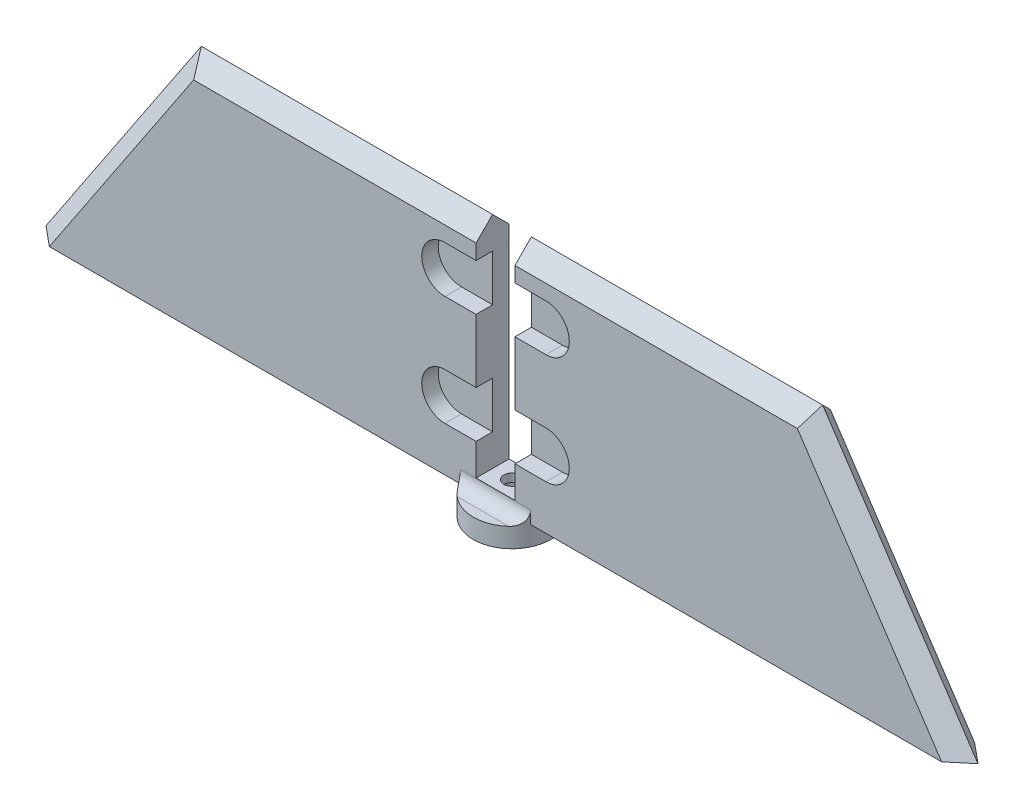
SolidWorks part; units mm, degrees
ref_plane "Alzado" through (0, 0, 0) normal (0, 0, 1) x (1, 0, 0)
ref_plane "Planta" through (0, 0, 0) normal (0, 1, 0) x (1, 0, 0)
ref_plane "Vista lateral" through (0, 0, 0) normal (1, 0, 0) x (0, 0, -1)
sketch "Croquis1" plane through (0, 0, 0) normal (0, 0, 1) x (1, 0, 0)
  line L0 (60, 0) -> (-60, 0)
  line L1 (-60, 0) -> (-40, 30)
  line L2 (-40, 30) -> (40, 30)
  line L3 (40, 30) -> (60, 0)
  point P4 (0, 0)
  dimension "D1" = 120
  dimension "D2" = 20
  dimension "3" = 30
  dimension "D3" = 20
extrude "Saliente-Extruir1" add sketch "Croquis1" along normal mid plane 4.25
sketch "Croquis2" plane through (0, 0, 0) normal (0, -1, 0) x (1, 0, 0)
  circle A0 centre (0, 0) radius 5
  dimension "D1" = 10
extrude "Saliente-Extruir2" add sketch "Croquis2" along normal blind 2.5
fillet "Redondeo1" radius 1.625 2 edges at (0, 0, -2.125) (0, 0, 2.125)
sketch "Sketch1" plane through (0, -2.5, 0) normal (0, -1, 0) x (1, 0, 0)
  circle A0 centre (0, 0) radius 2.45
  dimension "D1" = 4.9
extrude "Cut-Extrude1" cut sketch "Sketch1" against normal blind 3.1
chamfer "Chamfer1" distance 2.125 angle 45 6 edges at (50, 15, -2.125) (0, 30, -2.125) (-50, 15, -2.125) (50, 15, 2.125) (0, 30, 2.125) (-50, 15, 2.125)
sketch "Sketch2" plane through (0, 0, 2.125) normal (0, 0, 1) x (1, 0, 0)
  line L0 (0, 0.6) -> (0, 1.6) construction
  line L2 (-2.45, 0.6) -> (2.45, 0.6) construction
  line L10 (0, 1.6) -> (0, 30.1) construction
  line L12 (2.5, 1.6743) -> (-2.5, 1.6743)
  line L13 (2.5, 1.6743) -> (2.5, 30.0257)
  line L14 (2.5, 30.0257) -> (-2.5, 30.0257)
  line L15 (-2.5, 1.6743) -> (-2.5, 30.0257)
  line L16 (2.5, 1.6743) -> (-2.5, 30.0257) construction
  line L17 (2.5, 30.0257) -> (-2.5, 1.6743) construction
  point P9 (0, 15.85)
  dimension "D1" = 1
  dimension "D2" = 5
  dimension "D3" = 28.5
extrude "Cut-Extrude2" cut sketch "Sketch2" against normal through all both and the other way through all
sketch "Sketch3" plane through (0, 0.6, 0) normal (0, -1, 0) x (1, 0, 0)
  circle A0 centre (0, 0) radius 1.05
  dimension "D1" = 2.1
extrude "Cut-Extrude3" cut sketch "Sketch3" against normal through all both and the other way through all
sketch "Sketch4" plane through (0, 0, 2.125) normal (0, 0, 1) x (1, 0, 0)
  line L0 (0, 1.6743) -> (0, 30) construction
  line L1 (2.5, 1.6743) -> (-2.5, 1.6743) construction
  line L2 (0, 15.8372) -> (0, 30) construction
  line L3 (0, 15.8372) -> (0, 1.6743) construction
  line L4 (2.5, 15.8372) -> (2.5, 1.6743) construction
  line L5 (2.5, 27.875) -> (2.5, 1.6743) construction
  line L6 (2.5, 15.8372) -> (2.5, 30) construction
  line L7 (2.5, 22.9186) -> (6.5, 22.9186) construction
  line L8 (2.5, 8.7557) -> (6.5, 8.7557) construction
  line L9 (2.5, 8.7557) -> (6.5, 8.7557) construction
  line L10 (2.5, 11.7557) -> (6.5, 11.7557)
  line L11 (2.5, 5.7557) -> (6.5, 5.7557)
  line L12 (2.5, 22.9186) -> (6.5, 22.9186) construction
  line L13 (2.5, 25.9186) -> (6.5, 25.9186)
  line L14 (2.5, 19.9186) -> (6.5, 19.9186)
  line L15 (-2.5, 8.7557) -> (-6.5, 8.7557) construction
  line L16 (-2.5, 11.7557) -> (-6.5, 11.7557)
  line L17 (-2.5, 5.7557) -> (-6.5, 5.7557)
  line L18 (-2.5, 22.9186) -> (-6.5, 22.9186) construction
  line L19 (-2.5, 25.9186) -> (-6.5, 25.9186)
  line L20 (-2.5, 19.9186) -> (-6.5, 19.9186)
  line L21 (-2.5, 8.7557) -> (-6.5, 8.7557) construction
  line L22 (-2.5, 22.9186) -> (-6.5, 22.9186) construction
  line L23 (-2.5, 15.8372) -> (-2.5, 30) construction
  arc A0 (2.5, 11.7557) -> (2.5, 5.7557) centre (2.5, 8.7557) ccw
  arc A1 (6.5, 5.7557) -> (6.5, 11.7557) centre (6.5, 8.7557) ccw
  arc A2 (2.5, 25.9186) -> (2.5, 19.9186) centre (2.5, 22.9186) ccw
  arc A3 (6.5, 19.9186) -> (6.5, 25.9186) centre (6.5, 22.9186) ccw
  arc A4 (-2.5, 11.7557) -> (-2.5, 5.7557) centre (-2.5, 8.7557) cw
  arc A5 (-6.5, 5.7557) -> (-6.5, 11.7557) centre (-6.5, 8.7557) cw
  arc A6 (-2.5, 25.9186) -> (-2.5, 19.9186) centre (-2.5, 22.9186) cw
  arc A7 (-6.5, 19.9186) -> (-6.5, 25.9186) centre (-6.5, 22.9186) cw
  point P17 (4.5, 8.7557)
  point P22 (4.5, 22.9186)
  point P29 (-4.5, 8.7557)
  point P36 (-4.5, 22.9186)
  line M19 (-2.5, 1.6743) -> (-2.5, 27.875)
  line M29 (2.5, 27.875) -> (2.5, 1.6743)
  dimension "D4" = 3
  dimension "D1" = 4
  dimension "D2" = 14.1628
  dimension "D3" = 14.1628
extrude "Cut-Extrude4" cut sketch "Sketch4" against normal blind 2.125 and the other way through all contours L14 A3 L13 M29 | L11 A1 L10 M29 | A7 L20 L19 M19 | A5 L17 L16 M19
